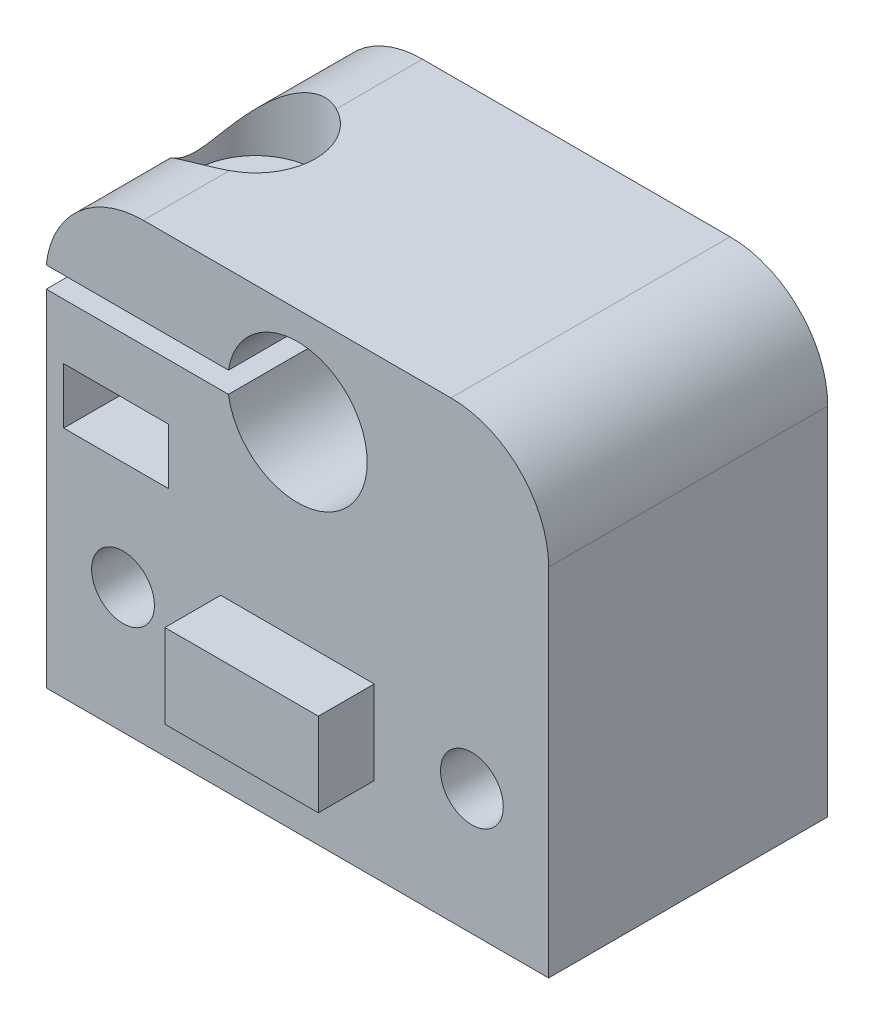
SolidWorks part; units mm, degrees
ref_plane "Спереди" through (0, 0, 0) normal (0, 0, 1) x (1, 0, 0)
ref_plane "Сверху" through (0, 0, 0) normal (0, 1, 0) x (1, 0, 0)
ref_plane "Справа" through (0, 0, 0) normal (1, 0, 0) x (0, 0, -1)
sketch "Эскиз1" plane through (0, 0, 0) normal (0, 1, 0) x (1, 0, 0)
  line L1 (0, 0) -> (36, 0)
  line L2 (0, 0) -> (0, 20)
  line L3 (0, 20) -> (36, 20)
  line L4 (36, 0) -> (36, 20)
  dimension "D1" = 20
  dimension "D2" = 36
extrude "Бобышка-Вытянуть1" add sketch "Эскиз1" along normal blind 32.5
sketch "Эскиз4" plane through (0, 0, 0) normal (0, 0, 1) x (1, 0, 0)
  line L1 (0, 0) -> (36, 0) construction
  line L2 (13.0566, 26.25) -> (-10.0973, 26.25)
  line L3 (-10.0973, 26.25) -> (-10.0973, 24.75)
  line L4 (-10.0973, 24.75) -> (13.0566, 24.75)
  circle A0 centre (18, 25.5) radius 5
  point P6 (18, 0)
  point P10 (-10.0973, 25.5)
  line M6 (0, 32.5) -> (0, 0)
  dimension "D1" = 10
  dimension "D2" = 25.5
  dimension "D3" = 1.5
extrude "Вырез-Вытянуть2" cut sketch "Эскиз4" against normal blind 47 contours A0 | A0 L2 L4 M6 region at (6.5094, 25.5, 0) region at (18, 25.5, 0)
sketch "Эскиз9" plane through (0, 0, 0) normal (0, 0, 1) x (1, 0, 0)
  line L0 (5.5, 9) -> (30.5, 9) construction
  line L1 (0, 0) -> (36, 0) construction
  circle A0 centre (30.5, 9) radius 2.25
  circle A1 centre (5.5, 9) radius 2.25
  point P4 (18, 9)
  point P7 (18, 0)
  dimension "D2" = 4.5
  dimension "D1" = 25
  dimension "D3" = 9
extrude "Вырез-Вытянуть7" cut sketch "Эскиз9" against normal blind 27
sketch "Эскиз10" plane through (0, 0, 0) normal (0, 0, 1) x (1, 0, 0)
  line L0 (0, 0) -> (36, 0) construction
  line L1 (23.5, 6) -> (12.5, 6)
  line L2 (23.5, 6) -> (23.5, 12)
  line L3 (23.5, 12) -> (12.5, 12)
  line L4 (12.5, 6) -> (12.5, 12)
  circle A0 centre (30.5, 9) radius 2.25 construction
  circle A1 centre (5.5, 9) radius 2.25 construction
  point P8 (23.5, 9)
  dimension "D1" = 6
  dimension "D2" = 7
  dimension "D3" = 7
  dimension "D4" = 9
extrude "Бобышка-Вытянуть2" add sketch "Эскиз10" along normal blind 4
sketch "Эскиз11" plane through (0, 32.5, 0) normal (0, 1, 0) x (1, 0, 0)
  line L0 (0, 20) -> (0, 0) construction
  circle A0 centre (5, 10) radius 2.25
  point P5 (0, 10)
  dimension "D1" = 4.5
  dimension "D2" = 5
extrude "Вырез-Вытянуть8" cut sketch "Эскиз11" against normal blind 20
sketch "Эскиз12" plane through (0, 32.5, 0) normal (0, 1, 0) x (1, 0, 0)
  circle A0 centre (5, 10) radius 4.3
  dimension "D1" = 8.6
extrude "Вырез-Вытянуть9" cut sketch "Эскиз12" against normal blind 5
sketch "Эскиз13" plane through (0, 0, -20) normal (0, 0, -1) x (-1, 0, 0)
  line L0 (0, 24.75) -> (0, 0) construction
  line L1 (-8.75, 20.75) -> (-1.25, 20.75)
  line L2 (-8.75, 20.75) -> (-8.75, 16.75)
  line L3 (-8.75, 16.75) -> (-1.25, 16.75)
  line L4 (-1.25, 20.75) -> (-1.25, 16.75)
  line L5 (0, 24.75) -> (-13.0566, 24.75) construction
  point P4 (-5, 20.75)
  dimension "D1" = 4
  dimension "D2" = 5
  dimension "D3" = 7.5
  dimension "D4" = 4
extrude "Вырез-Вытянуть10" cut sketch "Эскиз13" against normal blind 22
sketch "Эскиз14" plane through (0, 0, -20) normal (0, 0, -1) x (-1, 0, 0)
  circle A0 centre (-30.5, 9) radius 4.3
  circle A1 centre (-5.5, 9) radius 4.3
  dimension "D1" = 8.6
extrude "Вырез-Вытянуть11" cut sketch "Эскиз14" against normal blind 7
fillet "Скругление1" radius 7 2 edges at (36, 32.5, -10) (0, 32.5, -10)
